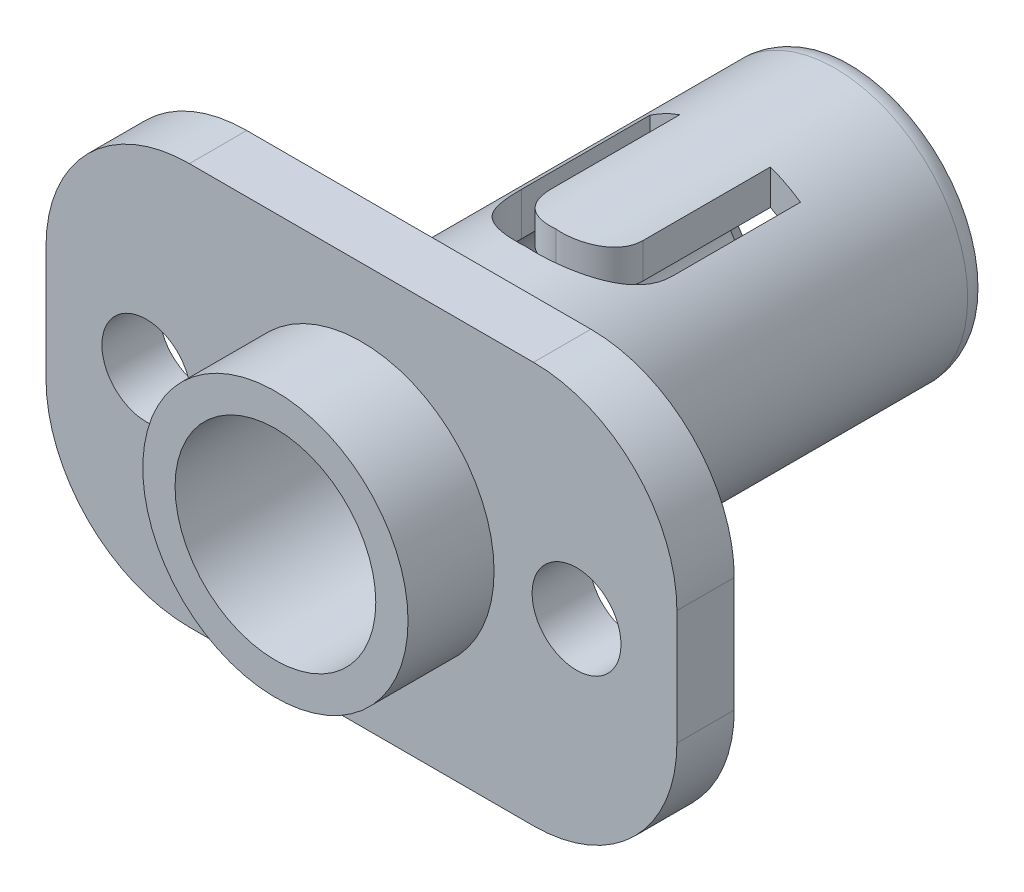
SolidWorks part; units mm, degrees
ref_plane "Plan de face" through (0, 0, 0) normal (0, 0, 1) x (1, 0, 0)
ref_plane "Plan de dessus" through (0, 0, 0) normal (0, 1, 0) x (1, 0, 0)
ref_plane "Plan de droite" through (0, 0, 0) normal (1, 0, 0) x (0, 0, -1)
sketch "Esquisse1" plane through (0, 0, 0) normal (0, 0, 1) x (1, 0, 0)
  line L1 (-12.6383, 12.4722) -> (9.3617, 12.4722)
  line L2 (-12.6383, 12.4722) -> (-12.6383, -1.5278)
  line L3 (-12.6383, -1.5278) -> (9.3617, -1.5278)
  line L4 (9.3617, 12.4722) -> (9.3617, -1.5278)
  dimension "D1" = 22
  dimension "D2" = 14
extrude "Boss.-Extru.1" add sketch "Esquisse1" along normal blind 2
ref_plane "Plan1" through (-1.6383, 0, 0) normal (-1, 0, 0) x (0, 0, 1)
ref_plane "Plan2" through (0, 5.4722, 0) normal (0, -1, 0) x (-1, 0, 0)
sketch "Esquisse3" plane through (0, 0, 0) normal (0, 0, -1) x (-1, 0, 0)
  line L0 (-1.1, 5.4722) -> (1.1, 5.4722) construction
  line L1 (1.6383, -1.1) -> (1.6383, 1.1) construction
  circle A0 centre (1.6383, 5.4722) radius 4.625
  circle A1 centre (1.6383, 5.4722) radius 3.5
  dimension "D1" = 9.25
extrude "Boss.-Extru.2" add sketch "Esquisse3" along normal blind 15
sketch "Esquisse5" plane through (0, 0, 2) normal (0, 0, 1) x (1, 0, 0)
  line L0 (-1.6383, 1.1) -> (-1.6383, -1.1) construction
  line L1 (-1.1, 5.4722) -> (1.1, 5.4722) construction
  circle A0 centre (-1.6383, 5.4722) radius 4.625
  dimension "D1" = 9.25
extrude "Boss.-Extru.3" add sketch "Esquisse5" along normal blind 3
sketch "Esquisse4" plane through (0, 0, 0) normal (0, 0, -1) x (-1, 0, 0)
  line L0 (-1.1, 5.4722) -> (1.1, 5.4722) construction
  line L1 (1.6383, -1.1) -> (1.6383, 1.1) construction
  circle A0 centre (1.6383, 5.4722) radius 3.5
extrude "Enlèv. mat.-Extru.1" cut sketch "Esquisse4" against normal through all
sketch "Esquisse6" plane through (0, 5.4722, 0) normal (0, -1, 0) x (-1, 0, 0)
  line L0 (3.217, 10.683) -> (4.265, 10.683)
  line L1 (4.265, 10.683) -> (4.265, 6.205)
  line L2 (3.217, 10.683) -> (3.217, 6.2357)
  line L3 (1.6383, 4.7901) -> (1.6383, 3.7375)
  line L4 (1.6383, 15) -> (1.6383, 0) construction
  arc A0 (4.265, 6.205) -> (1.6383, 3.7375) centre (1.7927, 6.205) cw
  arc A1 (3.217, 6.2357) -> (1.6383, 4.7901) centre (1.7657, 6.2357) cw
extrude "Enlèv. mat.-Extru.2" cut sketch "Esquisse6" against normal through all and the other way through all
mirror "Symétrie1" about plane through (-1.6383, 0, 0) normal (-1, 0, 0) of "Enlèv. mat.-Extru.2"
fillet "Congé1" radius 5 4 edges at (-12.6383, 12.4722, 1) (-12.6383, -1.5278, 1) (9.3617, -1.5278, 1) (9.3617, 12.4722, 1)
hole_wizard "Dégagement M2.51" positions "Esquisse8" profile "Esquisse9" hole size "M2.5" standard "ISO"
sketch "Esquisse8" plane through (0, 0, 0) normal (0, 0, -1) x (-1, 0, 0)
  line L0 (-1.1, 5.4722) -> (1.1, 5.4722) construction
  circle A0 centre (1.6383, 5.4722) radius 4.625 construction
  circle A1 centre (1.6383, 5.4722) radius 4.625 construction
  point P0 (-5.8617, 5.4722)
  point P4 (9.1383, 5.4722)
  dimension "D1" = 7.5
  dimension "D2" = 7.5
sketch "Esquisse9" plane through (5.8617, 5.4722, 0) normal (1, 0, 0) x (0, 1, 0)
  line L0 (0, 0) -> (0, 19.1013)
  line L1 (0, 19.1013) -> (1.55, 18.17)
  line L2 (1.55, 18.17) -> (1.55, 0)
  line L5 (1.55, 0) -> (0, 0)
  line L10 (0, 19.1013) -> (-1.55, 18.17) construction
  line L11 (0, -6.35) -> (0, 107.95) construction
  dimension "Diamètre du perçage" = 3.1
  dimension "Profondeur du perçage" = 18.17
  dimension "Angle de pointe" = 118
chamfer "Chanfrein1" distance 1 angle 45 1 edges at (-5.1383, 5.4722, -15)
fillet "Congé2" radius 1 1 edges at (-6.2633, 5.4722, -15)
ref_plane "Plan4" through (0, 1.9722, 0) normal (0, -1, 0) x (-1, 0, 0)
sketch "Esquisse12" plane through (0, 1.9722, 0) normal (0, -1, 0) x (-1, 0, 0)
  circle A0 centre (1.6262, 6.5) radius 1.5
extrude "Boss.-Extru.4" add sketch "Esquisse12" against normal blind 1.35 draft 32
mirror "Symétrie2" about plane through (0, 5.4722, 0) normal (0, -1, 0) of "Boss.-Extru.4"
